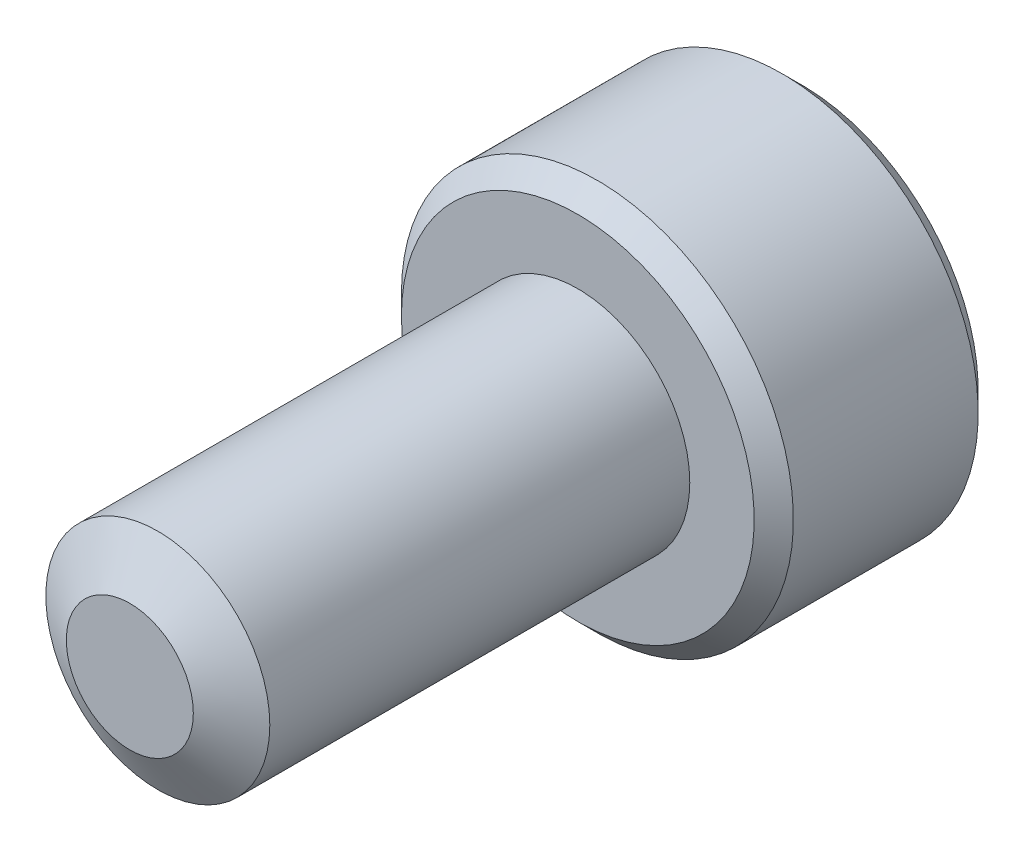
SolidWorks part; units mm, degrees
ref_plane "Front Plane" through (0, 0, 0) normal (0, 0, 1) x (1, 0, 0)
ref_plane "Top Plane" through (0, 0, 0) normal (0, 1, 0) x (1, 0, 0)
ref_plane "Right Plane" through (0, 0, 0) normal (1, 0, 0) x (0, 0, -1)
sketch "Sketch1" plane through (0, 0, 0) normal (0, 0, 1) x (1, 0, 0)
  circle A0 centre (0, 0) radius 2
  dimension "OD" = 4
extrude "Extrude1" add sketch "Sketch1" against normal blind 8
sketch "Sketch2" plane through (0, 0, 0) normal (0, 0, 1) x (1, 0, 0)
  circle A0 centre (0, 0) radius 2 construction
  circle A1 centre (0, 0) radius 2
curve "Helix/Spiral1" pitch 0.7 height 8.7 radius 2 centre (0, 0, 0) axis (0, 0, -1) start towards (0, 1, 0) parameters "pitch"=0.7
sketch "Sketch3" plane through (0, 0, 0) normal (1, 0, 0) x (0, 0, -1)
  line L0 (-0.6125, 2) -> (-0.35, 1.5453)
  line L1 (-0.35, 1.5453) -> (-0.2625, 1.5453)
  line L2 (-0.2625, 1.5453) -> (0, 2)
  line L3 (-0.6125, 2) -> (0, 2)
  line L4 (-0.3062, 2) -> (-0.3062, 1.5453) construction
  line L5 (-0.4812, 1.7727) -> (-0.1312, 1.7727) construction
  line L6 (0, 2) -> (0, -2) construction
  dimension "D1" = 0.0875
  dimension "D2" = 0.35
  dimension "D3" = 60
sweep "Cut-Sweep1" cut profiles "Sketch3" path "Helix/Spiral1" align with end faces yes
sketch "Sketch4" plane through (0, 0, 0) normal (1, 0, 0) x (0, 0, -1)
  line L0 (0.4962, 2) -> (0, 1.2913)
  line L1 (0, 1.2913) -> (0, 2)
  line L2 (0.4962, 2) -> (0, 2)
  line L3 (-0.6125, 2) -> (0, 2) construction
  line L4 (0, 0) -> (7.0209, 0) construction
  dimension "D1" = 55
  dimension "D2" = 0.254
revolve "Cut-Revolve1" cut sketch "Sketch4" angle 360 about L4
sketch "Sketch5" plane through (0, 0, 0) normal (1, 0, 0) x (0, 0, -1)
  line L0 (8, -0.6429) -> (8, 1.6418) construction
  line L1 (8, 2.127) -> (1.2679, 2.127)
  line L2 (8, 2.127) -> (8, 0)
  line L3 (8, 0) -> (1, 0)
  line L4 (1, 1.127) -> (1, 0)
  line L5 (1.2679, 2.127) -> (1, 1.127)
  line L6 (0, 0) -> (1, 0) construction
  point P3 (1, 2.127)
  point P10 (1, 2.127)
  dimension "D1" = 1
  dimension "D2" = 0.127
  dimension "D3" = 15
  dimension "Thread Min" = 1
revolve "partially thread" [suppressed] add sketch "Sketch5" angle 360 about L6
sketch "Sketch6" plane through (0, 0, -8) normal (0, 0, -1) x (-1, 0, 0)
  circle A0 centre (0, 0) radius 3.5
  dimension "head dia" = 7
extrude "Extrude2" add sketch "Sketch6" along normal blind 4
sketch "Sketch7" plane through (0, 0, -12) normal (0, 0, -1) x (-1, 0, 0)
  line L1 (0, 1.7321) -> (-1.5, 0.866)
  line L2 (-1.5, 0.866) -> (-1.5, -0.866)
  line L3 (-1.5, -0.866) -> (0, -1.7321)
  line L4 (0, -1.7321) -> (1.5, -0.866)
  line L5 (1.5, -0.866) -> (1.5, 0.866)
  line L6 (1.5, 0.866) -> (0, 1.7321)
  circle A0 centre (0, 0) radius 1.5 construction
  dimension "hex dia" = 3
extrude "Cut-Extrude1" cut sketch "Sketch7" against normal blind 2.25
sketch "Sketch8" plane through (0, 0, -12) normal (0, 0, -1) x (-1, 0, 0)
  circle A0 centre (0, 0) radius 1.7321
extrude "Cut-Extrude2" cut sketch "Sketch8" against normal through all draft 45
chamfer "Chamfer1" distance 0.35 angle 45 2 edges at (-3.5, 0, -12) (-3.5, 0, -8)
sketch "Sketch9" plane through (0, 0, 0) normal (1, 0, 0) x (0, 0, -1)
  line L0 (0, 2) -> (0, -2) construction
  line L1 (3.85, 2) -> (3.85, -2) construction
  dimension "D1" = 3.85
sketch "Sketch10" plane through (0, 0, 0) normal (0, 0, 1) x (1, 0, 0)
  circle A0 centre (0, 0) radius 2
  dimension "D1" = 4
extrude "Boss-Extrude1" add sketch "Sketch10" against normal up to surface (8 mm away) up to face at (-3.15, 0, -8)
chamfer "Chamfer2" distance 0.5 angle 60 1 edges at (2, 0, 0) first distance on face at (2, 0, -8)
equation "\"D3@Helix/Spiral1\" = \"screw length@Extrude1\"+\"pitch@Helix/Spiral1\""
equation "\"D1@Sketch3\" = \"pitch@Helix/Spiral1\"*.125"
equation "\"D2@Sketch3\" = \"pitch@Helix/Spiral1\"*.5"
equation "\"D1@Cut-Extrude1\" = \"hex dia@Sketch7\"*.75"
equation "\"D1@Chamfer1\" = \"head dia@Sketch6\"*.05"
equation "\"D1@Sketch9\" = \"pitch@Helix/Spiral1\"*5.5"
